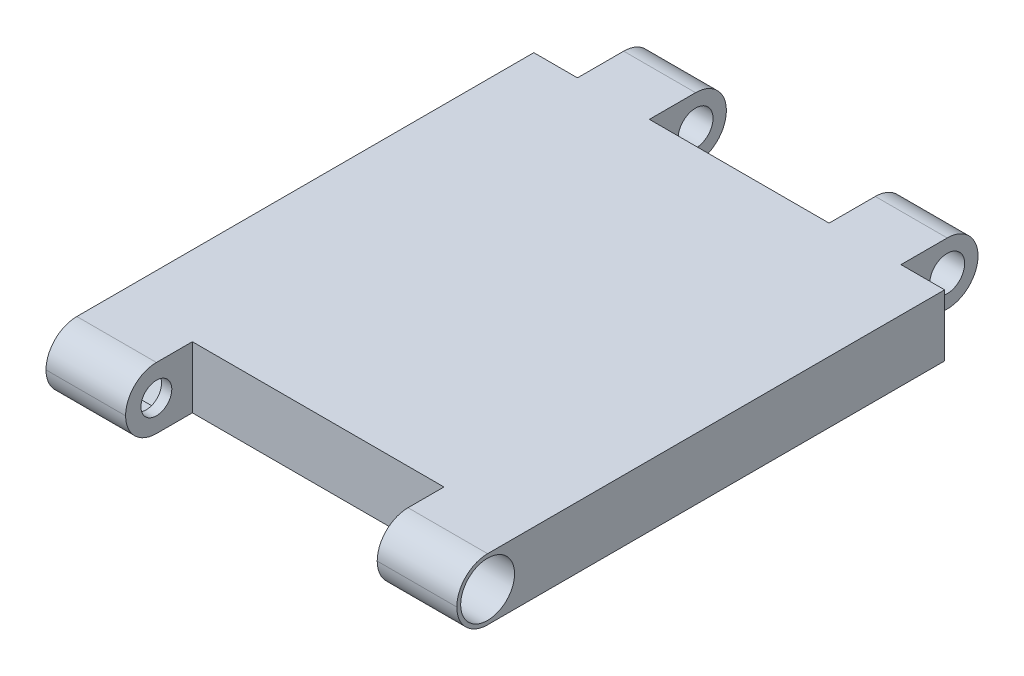
SolidWorks part; units mm, degrees
ref_plane "Front Plane" through (0, 0, 0) normal (0, 0, 1) x (1, 0, 0)
ref_plane "Top Plane" through (0, 0, 0) normal (0, 1, 0) x (1, 0, 0)
ref_plane "Right Plane" through (0, 0, 0) normal (1, 0, 0) x (0, 0, -1)
sketch "Sketch1" plane through (0, 0, 0) normal (0, 1, 0) x (1, 0, 0)
  line L0 (-40, 49) -> (40, 49) construction
  line L1 (-40, -55) -> (40, -55)
  line L2 (-40, -55) -> (-40, 55)
  line L3 (-40, 55) -> (40, 55)
  line L4 (40, -55) -> (40, 55)
  line L5 (-40, -55) -> (40, 55) construction
  line L6 (-40, 55) -> (40, -55) construction
  line L7 (-17.5, 55) -> (17.5, 55)
  line L8 (-17.5, 55) -> (-17.5, 40)
  line L9 (-17.5, 40) -> (17.5, 40)
  line L10 (17.5, 55) -> (17.5, 40)
  line L11 (-40, 55) -> (-31.5, 55)
  line L12 (-40, 55) -> (-40, 40)
  line L13 (-40, 40) -> (-31.5, 40)
  line L14 (-31.5, 55) -> (-31.5, 40)
  line L15 (40, 55) -> (31.5, 55)
  line L16 (40, 55) -> (40, 40)
  line L17 (40, 40) -> (31.5, 40)
  line L18 (31.5, 55) -> (31.5, 40)
  line L19 (0, -55) -> (0, 55) construction
  line L21 (-24.5, -42) -> (24.5, -42)
  line L22 (-24.5, -42) -> (-24.5, -55)
  line L23 (-24.5, -55) -> (24.5, -55)
  line L24 (24.5, -42) -> (24.5, -55)
  line L25 (-24.5, -42) -> (24.5, -55) construction
  line L26 (-24.5, -55) -> (24.5, -42) construction
  point P0 (0, 0)
  point P20 (0, -48.5)
  dimension "D1" = 80
  dimension "D2" = 110
  dimension "D3" = 14
  dimension "D4" = 14
  dimension "D5" = 8.5
  dimension "D6" = 8.5
  dimension "D7" = 6
  dimension "D8" = 9
  dimension "D9" = 9
  dimension "D10" = 9
  dimension "D11" = 13
  dimension "D12" = 49
  dimension "D13" = 35
extrude "Boss-Extrude1" add sketch "Sketch1" along normal blind 12 contours L18 L3 L10 L9 L8 L14 L13 L2 L1 L4 L17 region at (0, 0, 0.8337)
fillet "Fillet1" radius 6 4 edges at (-24.5, 0, -55) (-24.5, 12, -55) (24.5, 0, -55) (24.5, 12, -55)
sketch "Sketch2" plane through (40, 0, 0) normal (1, 0, 0) x (0, 0, -1)
  line L0 (-55, 6) -> (-49, 6) construction
  line L1 (-55, 12) -> (-55, 0) construction
  circle A0 centre (-49, 6) radius 5.25
  circle A1 centre (-49, 6) radius 3
  dimension "D2" = 10.5
  dimension "D3" = 6
  dimension "D1" = 6
extrude "Cut-Extrude1" cut sketch "Sketch2" along normal blind 2 from surface contours A1 region at (40, 6, 49) starting at face at (24.5, 6, 48.5)
extrude "Cut-Extrude2" cut sketch "Sketch2<4>" along normal blind 24 from surface contours A0 starting at face at (26.5, 6, 46)
sketch "Sketch2<4>" plane through (40, 0, 0) normal (1, 0, 0) x (0, 0, -1) same geometry as "Sketch2"
sketch "Sketch3" plane through (-40, 0, 0) normal (-1, 0, 0) x (0, 0, 1)
  line L0 (55, 12) -> (-40, 12) construction
  line L1 (53.792, 6) -> (51.396, 10.15)
  line L2 (51.396, 10.15) -> (46.604, 10.15)
  line L3 (46.604, 10.15) -> (44.208, 6)
  line L4 (44.208, 6) -> (46.604, 1.85)
  line L5 (46.604, 1.85) -> (51.396, 1.85)
  line L6 (51.396, 1.85) -> (53.792, 6)
  circle A0 centre (49, 6) radius 4.15 construction
  circle A1 centre (49, 6) radius 3
  dimension "D1" = 8.3
  dimension "D2" = 6
extrude "Cut-Extrude3" cut sketch "Sketch3" along normal blind 2 from surface contours A1 region at (-40, 6, 49) starting at face at (-24.5, 6, 48.5)
extrude "Cut-Extrude4" cut sketch "Sketch3<3>" along normal blind 23 from surface contours L2 L3 L4 L5 L6 L1 starting at face at (-26.5, 6, 46)
sketch "Sketch3<3>" plane through (-40, 0, 0) normal (-1, 0, 0) x (0, 0, 1) same geometry as "Sketch3"
sketch "Sketch4" plane through (-31.5, 0, 0) normal (-1, 0, 0) x (0, 0, 1)
  line L0 (-55, 6) -> (-49, 6) construction
  arc A0 (-49, 12) -> (-55, 6) centre (-49, 6) ccw construction
  circle A1 centre (-49, 6) radius 3.4
  dimension "D1" = 6.8
extrude "Cut-Extrude5" cut sketch "Sketch4" against normal blind 92 contours A1
fillet "Fillet2" radius 6 4 edges at (32.25, 0, 55) (32.25, 12, 55) (-32.25, 0, 55) (-32.25, 12, 55)
